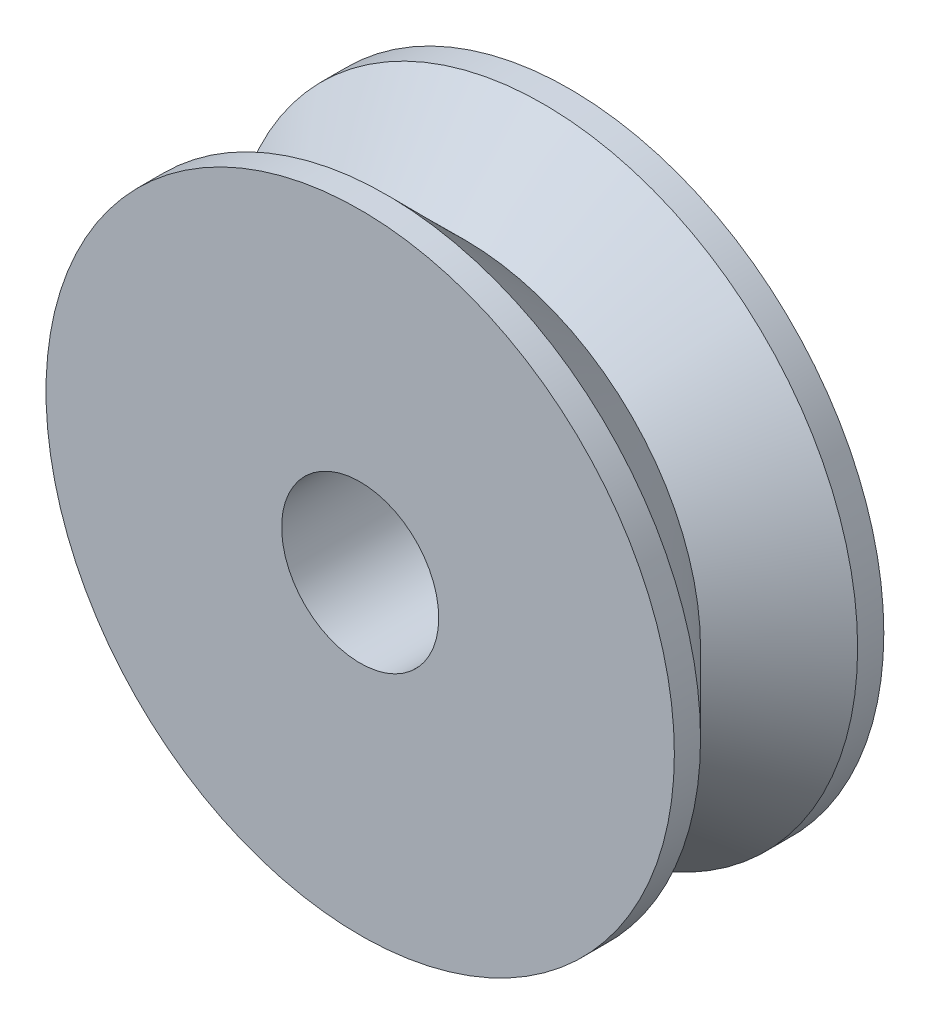
SolidWorks part; units mm, degrees
ref_plane "Front Plane" through (0, 0, 0) normal (0, 0, 1) x (1, 0, 0)
ref_plane "Top Plane" through (0, 0, 0) normal (0, 1, 0) x (1, 0, 0)
ref_plane "Right Plane" through (0, 0, 0) normal (1, 0, 0) x (0, 0, -1)
sketch "Sketch1" plane through (0, 0, 0) normal (0, 0, 1) x (1, 0, 0)
  circle A0 centre (0, 0) radius 6
  circle A1 centre (0, 0) radius 1.5
extrude "Boss-Extrude1" add sketch "Sketch1" along normal blind 2
chamfer "Chamfer1" distance 1.5 angle 45 1 edges at (6, 0, 2)
sketch "Sketch2" plane through (0, 0, 2) normal (0, 0, 1) x (1, 0, 0)
  circle A0 centre (0, 0) radius 6
  circle A1 centre (0, 0) radius 1.5
extrude "Boss-Extrude2" add sketch "Sketch2" along normal blind 2
chamfer "Chamfer2" distance 1.5 angle 45 1 edges at (6, 0, 2)
